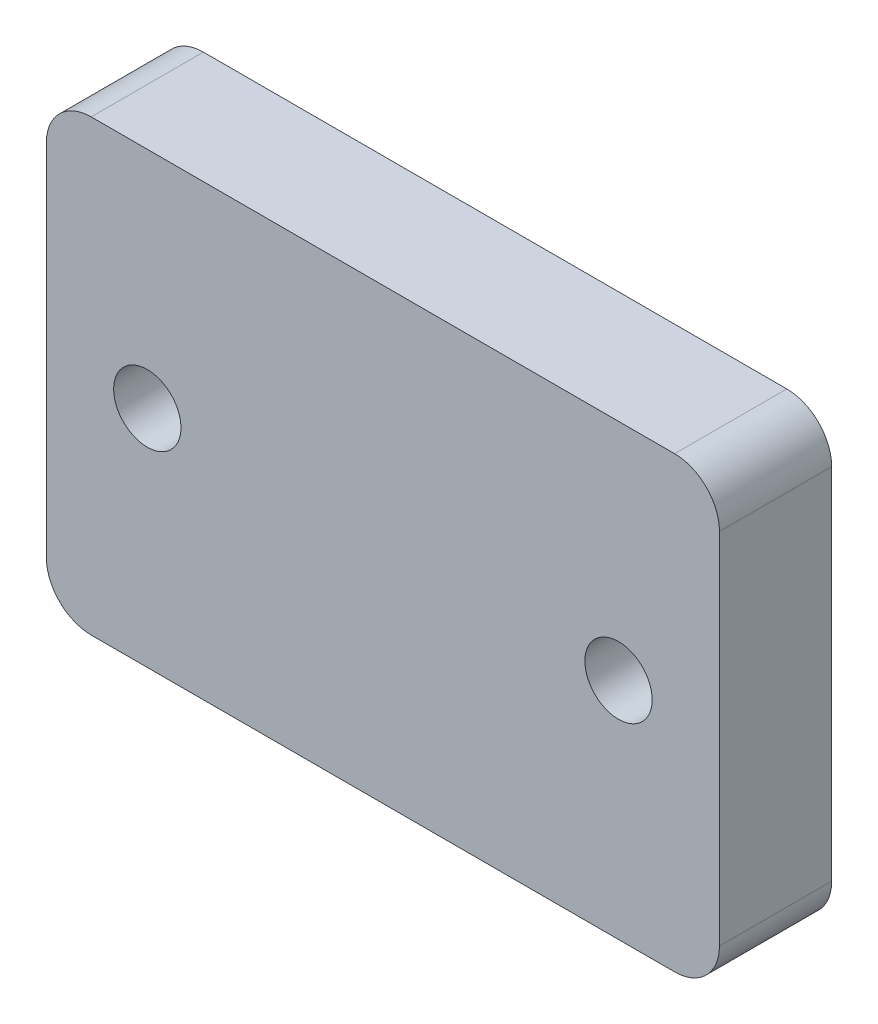
SolidWorks part; units mm, degrees
ref_plane "前视基准面" through (0, 0, 0) normal (0, 0, 1) x (1, 0, 0)
ref_plane "上视基准面" through (0, 0, 0) normal (0, 1, 0) x (1, 0, 0)
ref_plane "右视基准面" through (0, 0, 0) normal (1, 0, 0) x (0, 0, -1)
sketch "草图1" plane through (0, 0, 0) normal (0, 0, 1) x (1, 0, 0)
  line L1 (15, -10) -> (-15, -10)
  line L2 (15, -10) -> (15, 10)
  line L3 (15, 10) -> (-15, 10)
  line L4 (-15, -10) -> (-15, 10)
  line L5 (15, -10) -> (-15, 10) construction
  line L6 (15, 10) -> (-15, -10) construction
  point P0 (0, 0)
  dimension "D1" = 30
  dimension "D2" = 20
extrude "凸台-拉伸1" add sketch "草图1" along normal blind 5
sketch "草图3" plane through (0, 0, 5) normal (0, 0, 1) x (1, 0, 0)
  line L0 (0, 0) -> (10.5, 0) construction
  line L1 (0, -55) -> (0, 55) construction
  circle A0 centre (10.5, 0) radius 1.5
  circle A1 centre (-10.5, 0) radius 1.5
  dimension "D1" = 10.5
  dimension "D2" = 3
extrude "切除-拉伸2" cut sketch "草图3" against normal through all
fillet "圆角1" radius 2 4 edges at (15, -10, 2.5) (15, 10, 2.5) (-15, 10, 2.5) (-15, -10, 2.5)
